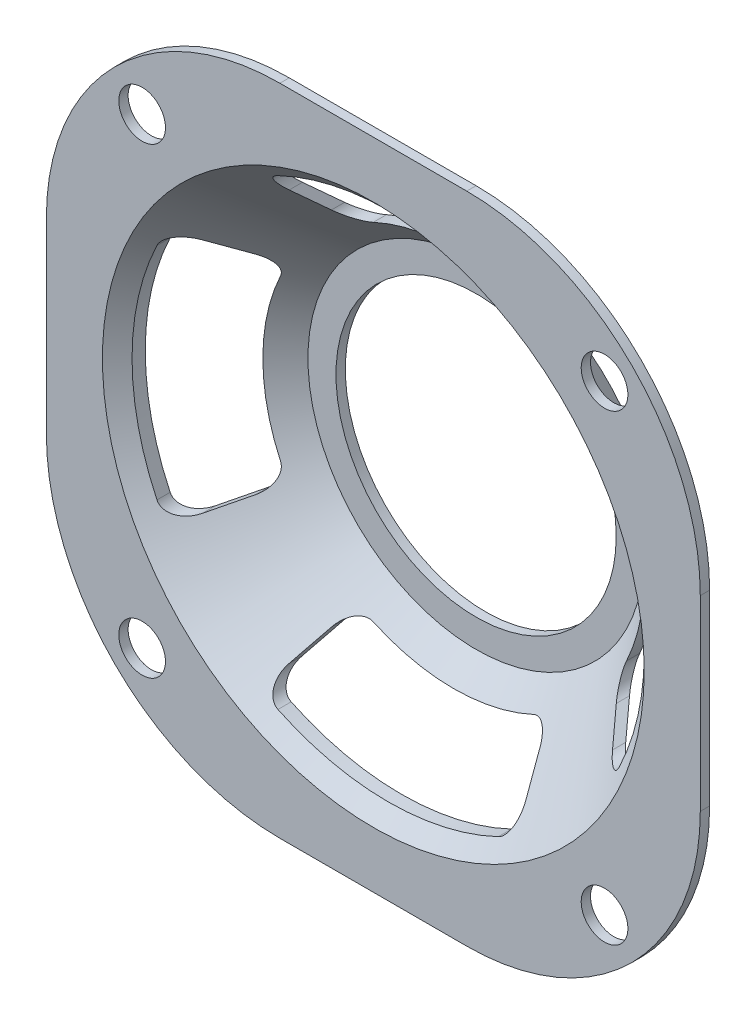
SolidWorks part; units mm, degrees
ref_plane "Front" through (0, 0, 0) normal (0, 0, 1) x (1, 0, 0)
ref_plane "Top" through (0, 0, 0) normal (0, 1, 0) x (1, 0, 0)
ref_plane "Right" through (0, 0, 0) normal (1, 0, 0) x (0, 0, -1)
other "Configuration Table"
sketch "Sketch1" plane through (0, 0, 0) normal (0, 0, 1) x (1, 0, 0)
  line L0 (35, -35) -> (-35, 35) construction
  line L1 (-10, -35) -> (10, -35)
  line L2 (-35, -10) -> (-35, 10)
  line L3 (-10, 35) -> (10, 35)
  line L4 (35, -10) -> (35, 10)
  arc A0 (-35, 10) -> (-10, 35) centre (-10, 10) cw
  arc A1 (10, 35) -> (35, 10) centre (10, 10) cw
  arc A2 (-10, -35) -> (-35, -10) centre (-10, -10) cw
  arc A3 (10, -35) -> (35, -10) centre (10, -10) ccw
  point P13 (-35, -35)
  dimension "D2" = 25
  dimension "D1" = 70
  dimension "D4" = 70
extrude "Extrude1" add sketch "Sketch1" against normal blind 1
ref_axis "Axis1" through (0, 0, 0.6) along (0, 0, -1)
sketch "Sketch6" plane through (0, 0, -1) normal (0, 0, -1) x (-1, 0, 0)
  circle A0 centre (0, 0) radius 30
  dimension "D1" = 60
extrude "Cut-Extrude1" cut sketch "Sketch6" against normal through all
sketch "Sketch7" plane through (0, 0, -1) normal (0, 0, -1) x (-1, 0, 0)
  line L0 (-24.7487, -24.7487) -> (24.7487, 24.7487) construction
  line L1 (-24.7487, 24.7487) -> (24.7487, -24.7487) construction
  circle A1 centre (-24.7487, 24.7487) radius 2.5
  circle A2 centre (24.7487, 24.7487) radius 2.5
  circle A3 centre (24.7487, -24.7487) radius 2.5
  circle A4 centre (-24.7487, -24.7487) radius 2.5
  arc A5 (-10, 35) -> (-35, 10) centre (-10, 10) ccw construction
  point P4 (-10, 10)
  dimension "D2" = 5
  dimension "D1" = 90
  dimension "D3" = 70
extrude "Cut-Extrude3" cut sketch "Sketch7" against normal through all
sketch "Sketch8" plane through (0, 0, 0) normal (1, 0, 0) x (0, 0, -1)
  line L0 (0, 30) -> (0, 29)
  line L5 (0, 29) -> (11, 18)
  line L6 (11, 18) -> (11, 15)
  line L7 (0, 0) -> (13.0042, 0) construction
  line L8 (1, 10) -> (1, 35) construction
  dimension "D1" = 3
  dimension "D2" = 1
  dimension "D3" = 135
  dimension "D4" = 10
revolve "Revolve-Thin1" add sketch "Sketch8" angle 360 about L7 wall 1
sketch "Sketch9" plane through (0, 0, -12) normal (0, 0, -1) x (-1, 0, 0)
  line L0 (11.1624, 19.3338) -> (12.6677, 21.9411)
  line L1 (-11.1624, 19.3338) -> (-12.6677, 21.9411)
  line L2 (0, 0) -> (0, 27.4142) construction
  arc A0 (-12.6677, 21.9411) -> (-11.7962, 24.7465) centre (-10.9356, 22.9411) cw
  arc A1 (-11.1624, 19.3338) -> (-8.5889, 18.5195) centre (-9.4304, 20.3338) ccw
  circle A2 centre (0, 0) radius 20.4142
  arc A3 (8.5889, 18.5195) -> (-8.5889, 18.5195) centre (0, 0) ccw
  arc A4 (12.6677, 21.9411) -> (11.7962, 24.7465) centre (10.9356, 22.9411) ccw
  arc A5 (11.1624, 19.3338) -> (8.5889, 18.5195) centre (9.4304, 20.3338) cw
  circle A6 centre (0, 0) radius 27.4142
  arc A7 (11.7962, 24.7465) -> (-11.7962, 24.7465) centre (0, 0) ccw
  dimension "D4" = 2
  dimension "D3" = 60
  dimension "D1" = 2
  dimension "D2" = 2
extrude "Cut-Extrude4" cut sketch "Sketch9" against normal through all
pattern_circular "CirPattern1" count 4 over 360 about axis through (0, 0, 0) along (0, 0, -1) of "Cut-Extrude4"
equation "\"D4@Sketch1\"=\"D1@Sketch1\""
equation "\"D3@Sketch7\" = \"D1@Sketch1\""
